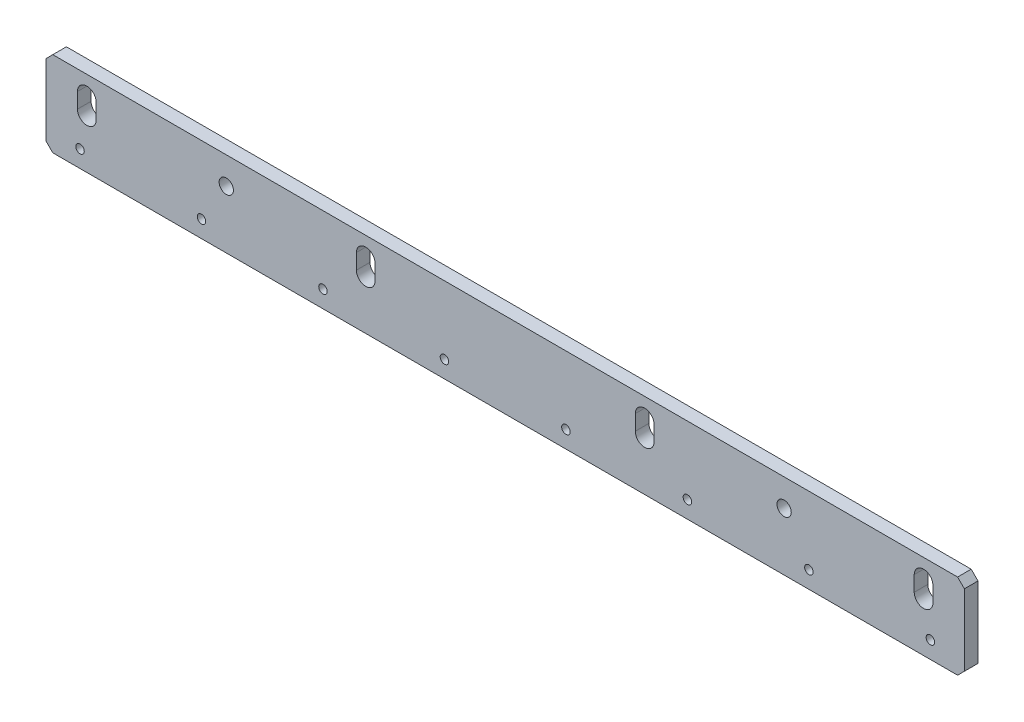
SolidWorks part; units mm, degrees
material "3.3315 (EN-AW 5005)"
ref_plane "Front Plane" through (0, 0, 0) normal (0, 0, 1) x (1, 0, 0)
ref_plane "Top Plane" through (0, 0, 0) normal (0, 1, 0) x (1, 0, 0)
ref_plane "Right Plane" through (0, 0, 0) normal (1, 0, 0) x (0, 0, -1)
sketch "Sketch1" plane through (0, 0, 0) normal (0, 0, 1) x (1, 0, 0)
  line L1 (135, -12.5) -> (-135, -12.5)
  line L2 (135, -12.5) -> (135, 12.5)
  line L3 (135, 12.5) -> (-135, 12.5)
  line L4 (-135, -12.5) -> (-135, 12.5)
  line L5 (135, -12.5) -> (-135, 12.5) construction
  line L6 (135, 12.5) -> (-135, -12.5) construction
  point P0 (0, 0)
  dimension "D1" = 270
  dimension "D2" = 25
extrude "Boss-Extrude1" add sketch "Sketch1" along normal blind 4
hole_wizard "M5 Clearance Slot1" positions "Sketch2" profile "Sketch3" size "M5" standard "ISO" slot yes end condition through all
sketch "Sketch2" plane through (0, 0, 4) normal (0, 0, 1) x (1, 0, 0)
  line L0 (-123, -0.5) -> (-123, 9.5) construction
  line L1 (-135, 12.5) -> (-135, -12.5) construction
  line L2 (135, 12.5) -> (-135, 12.5) construction
  point P0 (-123, 4.5)
  dimension "D1" = 10
  dimension "D2" = 12
  dimension "D3" = 3
sketch "Sketch3" plane through (-123, 4.5, 4) normal (1, 0, 0) x (0, -1, 0)
  line L0 (0, 0) -> (0, 4)
  line L1 (0, 4) -> (2.75, 4)
  line L2 (2.75, 4) -> (2.75, 0)
  line L5 (2.75, 0) -> (0, 0)
  line L11 (0, -6.35) -> (0, 107.95) construction
  dimension "Thru Hole Dia." = 5.5
  dimension "Thru Hole Depth" = 4
pattern_linear "LPattern1" count 4 spacing 82 along (1, 0, 0) of "M5 Clearance Slot1"
hole_wizard "M3 Tapped Hole1" positions "Sketch4" profile "Sketch5" tap size "M3" standard "ISO" end condition through all
sketch "Sketch4" plane through (0, 0, 4) normal (0, 0, 1) x (1, 0, 0)
  line L0 (-135, 12.5) -> (-135, -12.5) construction
  line L1 (-135, -12.5) -> (135, -12.5) construction
  point P0 (-125, -7.5)
  dimension "D1" = 10
  dimension "D2" = 5
sketch "Sketch5" plane through (-125, -7.5, 4) normal (1, 0, 0) x (0, -1, 0)
  line L0 (0, 0) -> (0, 4)
  line L1 (0, 4) -> (1.25, 4)
  line L2 (1.25, 4) -> (1.25, 0)
  line L5 (1.25, 0) -> (0, 0)
  line L11 (0, -6.35) -> (0, 107.95) construction
  dimension "Thru Tap Drill Dia." = 2.5
  dimension "Thru Tap Drill Depth" = 4
cosmetic thread "Hole Thread17" parameters "D2"=3
pattern_linear "LPattern2" count 8 spacing 35.7143 along (1, 0, 0) of "M3 Tapped Hole1"
cosmetic thread "Hole Thread18" parameters "D2"=3
cosmetic thread "Hole Thread19" parameters "D2"=3
cosmetic thread "Hole Thread20" parameters "D2"=3
cosmetic thread "Hole Thread21" parameters "D2"=3
cosmetic thread "Hole Thread22" parameters "D2"=3
cosmetic thread "Hole Thread23" parameters "D2"=3
cosmetic thread "Hole Thread24" parameters "D2"=3
chamfer "Chamfer1" distance 2 angle 45 4 edges at (135, -12.5, 2) (135, 12.5, 2) (-135, -12.5, 2) (-135, 12.5, 2)
sketch "Sketch6" plane through (0, 0, 4) normal (0, 0, 1) x (1, 0, 0)
  line L0 (82, 4.5) -> (120.25, 4.5) construction
  line L1 (120.25, 2.25) -> (120.25, 6.75) construction
  line L2 (43.75, 4.5) -> (82, 4.5) construction
  line L3 (43.75, 2.25) -> (43.75, 6.75) construction
  circle A0 centre (82, 4.5) radius 6
  dimension "D1" = 12
hole_wizard "M5 Tapped Hole1" positions "Sketch7" profile "Sketch8" tap size "M5" standard "ISO" end condition through all
sketch "Sketch7" plane through (0, 0, 4) normal (0, 0, 1) x (1, 0, 0)
  line L0 (-82, 4.5) -> (-43.75, 4.5) construction
  line L1 (-43.75, 2.25) -> (-43.75, 6.75) construction
  line L3 (0, 0) -> (0, 37.425) construction
  line L5 (-82, 4.5) -> (-120.25, 4.5) construction
  line L6 (-120.25, 2.25) -> (-120.25, 6.75) construction
  point P0 (82, 4.5)
  point P2 (-82, 4.5)
sketch "Sketch8" plane through (82, 4.5, 4) normal (1, 0, 0) x (0, -1, 0)
  line L0 (0, 0) -> (0, 4)
  line L1 (0, 4) -> (2.1, 4)
  line L2 (2.1, 4) -> (2.1, 0)
  line L5 (2.1, 0) -> (0, 0)
  line L11 (0, -6.35) -> (0, 107.95) construction
  dimension "Thru Tap Drill Dia." = 4.2
  dimension "Thru Tap Drill Depth" = 4
cosmetic thread "Hole Thread25" parameters "D2"=5
cosmetic thread "Hole Thread26" parameters "D2"=5
